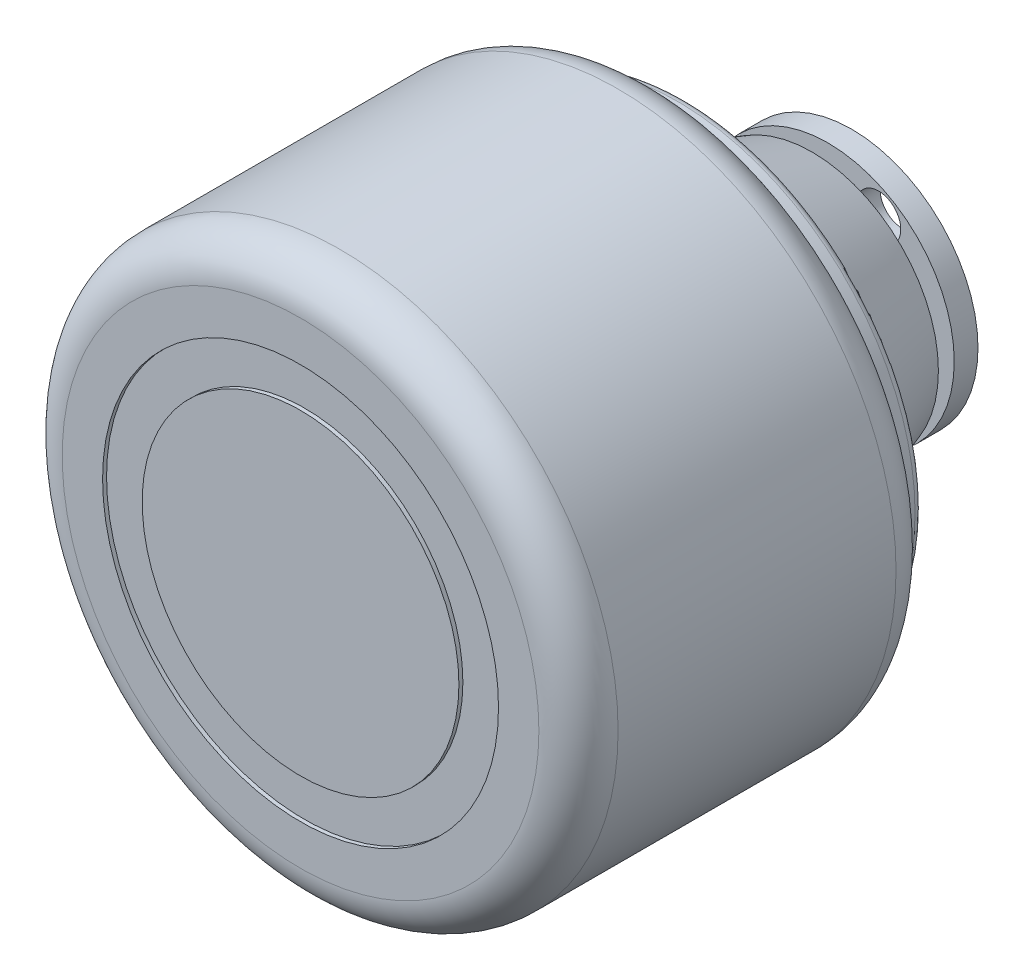
SolidWorks part; units mm, degrees
ref_plane "정면" through (0, 0, 0) normal (0, 0, 1) x (1, 0, 0)
ref_plane "윗면" through (0, 0, 0) normal (0, 1, 0) x (1, 0, 0)
ref_plane "우측면" through (0, 0, 0) normal (1, 0, 0) x (0, 0, -1)
sketch "스케치1" plane through (0, 0, 0) normal (0, 0, 1) x (1, 0, 0)
  circle A0 centre (0, 0) radius 35.1
  dimension "D1" = 70.2
extrude "보스-돌출1" add sketch "스케치1" along normal blind 45.1
sketch "스케치3" plane through (0, 0, 0) normal (0, 0, 1) x (1, 0, 0)
  circle A0 centre (0, 0) radius 30
  circle A1 centre (0, 0) radius 20
  dimension "D1" = 60
  dimension "D2" = 40
extrude "보스-돌출2" add sketch "스케치3" against normal blind 3.5
extrude "보스-돌출3" add sketch "스케치3<4>" against normal blind 24.5 contours A1 region at (0, 0, 0)
sketch "스케치3<4>" plane through (0, 0, 0) normal (0, 0, 1) x (1, 0, 0) same geometry as "스케치3"
sketch "스케치4" plane through (0, 0, 0) normal (0, 1, 0) x (1, 0, 0)
  line L0 (-20, 24.5) -> (-20, 3.5)
  line L1 (20, 3.5) -> (20, 24.5)
  line L2 (20, 3.5) -> (20, 24.5)
  line L3 (-20, 24.5) -> (-20, 3.5)
  line L4 (-20, 24.5) -> (20, 24.5)
  line L5 (-20, 24.5) -> (20, 24.5)
  line L6 (0, 24.5) -> (0, 48.1094) construction
  line L7 (0, 24.5) -> (-15.95, 24.5)
  line L8 (0, 24.5) -> (4.7223, 24.5)
  line L9 (-15.95, 24.5) -> (-15.95, 21.5)
  line L10 (-15.95, 21.5) -> (0, 21.5)
  line L11 (0, 24.5) -> (0, 8.001) construction
  line L12 (0, 21.5) -> (0, 19.5)
  line L13 (0, 19.5) -> (-15.95, 19.5)
  line L14 (-15.95, 19.5) -> (-20, 7.5)
  line L15 (-4, 21.5) -> (-4, 19.5)
  point P18 (15.95, 24.5)
  dimension "D1" = 15.95
  dimension "D2" = 3
  dimension "D3" = 15.95
  dimension "D4" = 4
  dimension "D5" = 2
  dimension "D6" = 4
sketch "스케치5" plane through (0, 0, -24.5) normal (0, 0, -1) x (-1, 0, 0)
  circle A0 centre (0, 0) radius 15.95
  dimension "D1" = 31.9
revolve "컷-회전2" cut sketch "스케치4" angle 360 about L6 region at (-17.975, 0, -24.2665)
fillet "필렛1" radius 5 2 edges at (35.1, 0, 45.1) (35.1, 0, 0)
fillet "필렛2" radius 20 1 edges at (20, 0, -7.5)
fillet "필렛3" radius 1 1 edges at (30, 0, -3.5)
sketch "스케치6" plane through (0, 0, -24.5) normal (0, 0, -1) x (-1, 0, 0)
  circle A0 centre (0, 0) radius 12.8
  circle A1 centre (12.8, 0) radius 2.8
  circle A2 centre (-6.4, -11.0851) radius 2.8
  circle A3 centre (-6.4, 11.0851) radius 2.8
  point P12 (0, 0)
  dimension "D1" = 25.6
  dimension "D2" = 5.6
  dimension "D3" = 3
extrude "컷-돌출1" cut sketch "스케치6" against normal blind 4 contours A0 A1 | A0 A1 | A0 A3 | A0 A3 | A0 A2 | A0 A2 region at (-11.5582, 0, -24.5) region at (-13.9315, 0, -24.5) region at (5.7791, 10.0097, -24.5) region at (6.9657, 12.065, -24.5) region at (6.9657, -12.065, -24.5) region at (5.7791, -10.0097, -24.5)
sketch "스케치7" plane through (0, 0, 45.1) normal (0, 0, 1) x (1, 0, 0)
  circle A0 centre (0, 0) radius 25
  circle A1 centre (0, 0) radius 20
  dimension "D1" = 40
  dimension "D2" = 50
extrude "컷-돌출2" cut sketch "스케치7" against normal blind 0.5
